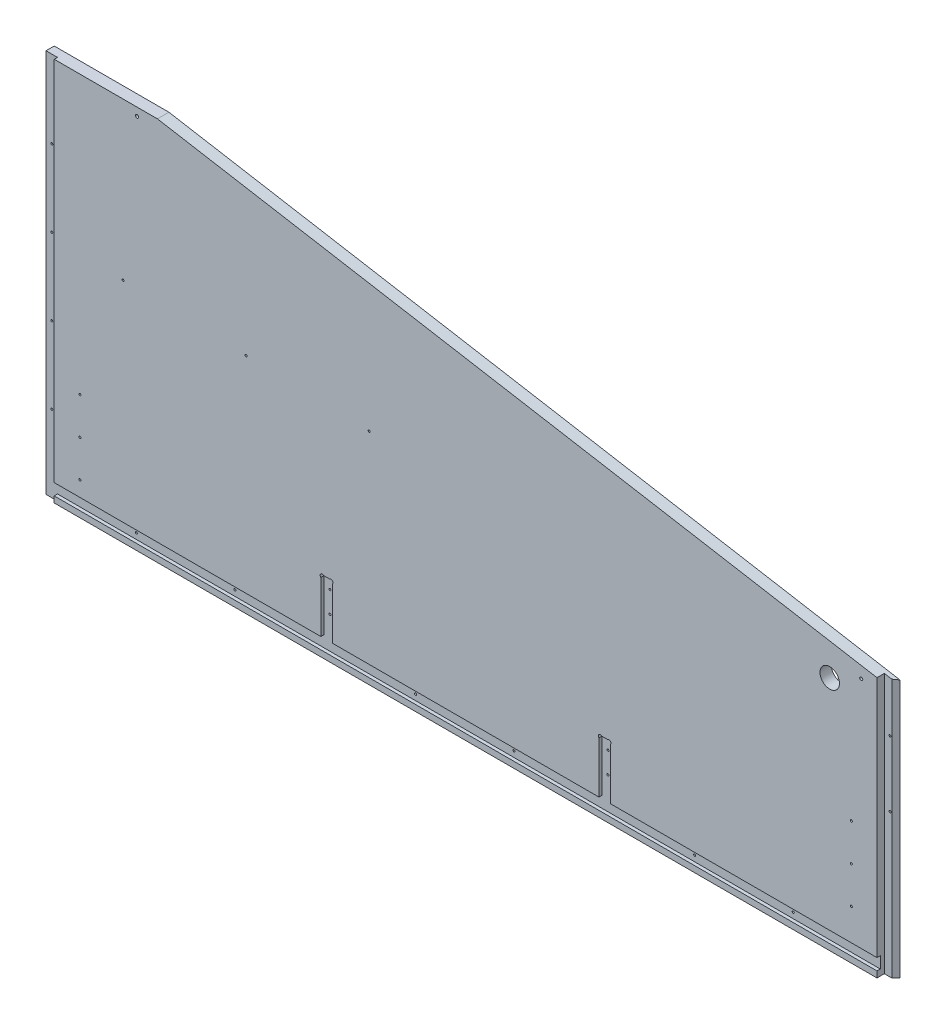
SolidWorks part; units mm, degrees
material "Maple"
ref_plane "Front Plane" through (0, 0, 0) normal (0, 0, 1) x (1, 0, 0)
ref_plane "Top Plane" through (0, 0, 0) normal (0, 1, 0) x (1, 0, 0)
ref_plane "Right Plane" through (0, 0, 0) normal (1, 0, 0) x (0, 0, -1)
sketch "Sketch1" plane through (0, 0, 0) normal (0, 0, 1) x (1, 0, 0)
  line L0 (8932.6508, -5243.5125) -> (10226.1458, -5243.5125)
  line L1 (9086.3208, -4722.0918) -> (10222.9708, -4853.7812)
  line L2 (8914.8708, -6342.0625) -> (10197.5708, -6342.0625)
  line L3 (8914.8708, -5808.6625) -> (10197.5708, -5808.6625)
  line L4 (8919.6333, -5253.0375) -> (10218.2083, -5253.0375)
  line L5 (9134.2633, -4656.1375) -> (9134.2633, -4638.3575)
  line L6 (9091.0833, -4638.3575) -> (9134.2633, -4638.3575)
  line L7 (9091.0833, -4567.2375) -> (9091.0833, -4638.3575)
  line L8 (9134.2633, -4656.1375) -> (9581.3033, -4656.1375)
  line L9 (9091.0833, -4567.2375) -> (9624.4833, -4567.2375)
  line L10 (9581.3033, -4656.1375) -> (9581.3033, -4638.3575)
  line L11 (9581.3033, -4638.3575) -> (9624.4833, -4638.3575)
  line L12 (9624.4833, -4567.2375) -> (9624.4833, -4638.3575)
  line L13 (8932.6508, -5225.7325) -> (9344.9775, -5225.7325)
  line L14 (8932.6508, -5256.2125) -> (8932.6508, -5243.5125)
  line L15 (8911.6958, -5256.2125) -> (8932.6508, -5256.2125)
  line L16 (8914.8708, -4722.0918) -> (9086.3208, -4722.0918)
  line L17 (8911.6958, -4715.5913) -> (8932.6508, -4715.5913)
  line L18 (8914.8708, -6342.0625) -> (8914.8708, -5808.6625)
  line L19 (12082.9917, -4722.0918) -> (10946.3417, -4853.7812)
  line L20 (12236.6617, -5243.5125) -> (10943.1667, -5243.5125)
  line L21 (10951.1042, -5253.0375) -> (12249.6792, -5253.0375)
  line L22 (10838.3917, -5656.2625) -> (11308.2917, -5656.2625)
  line L23 (10838.3917, -5719.7625) -> (11308.2917, -5719.7625)
  line L24 (10838.3917, -5742.5368) -> (11308.2917, -5742.5368)
  line L25 (10806.6417, -6342.0625) -> (11340.0417, -6342.0625)
  line L26 (10803.4667, -6335.7125) -> (11343.2167, -6335.7125)
  line L27 (10803.4667, -6317.9325) -> (11343.2167, -6317.9325)
  line L28 (10943.1667, -5225.7325) -> (11376.4483, -5225.7325)
  line L29 (11506.7292, -4754.5625) -> (10806.6417, -4827.5875)
  line L30 (11506.7292, -4567.2375) -> (11506.7292, -4754.5625)
  line L31 (10806.6417, -4567.2375) -> (10806.6417, -4827.5875)
  line L32 (10806.6417, -4567.2375) -> (11506.7292, -4567.2375)
  line L33 (10235.6708, -6329.3625) -> (10245.1958, -6329.3625)
  line L34 (10245.1958, -6329.3625) -> (10254.7208, -6278.5625)
  line L35 (10302.3458, -6329.3625) -> (10311.8708, -6278.5625)
  line L36 (10302.3458, -6329.3625) -> (10292.8208, -6329.3625)
  line L37 (10245.1958, -5821.3625) -> (10254.7208, -5872.1625)
  line L38 (10235.6708, -5821.3625) -> (10245.1958, -5821.3625)
  line L39 (10292.8208, -5821.3625) -> (10302.3458, -5821.3625)
  line L40 (10302.3458, -5821.3625) -> (10311.8708, -5872.1625)
  line L41 (10235.6708, -5821.3625) -> (10235.6708, -6329.3625)
  line L42 (10254.7208, -5872.1625) -> (10254.7208, -6278.5625)
  line L43 (10311.8708, -5872.1625) -> (10311.8708, -6278.5625)
  line L44 (10292.8208, -5821.3625) -> (10292.8208, -6329.3625)
  line L45 (8932.6508, -5225.7325) -> (8932.6508, -4715.5913)
  line L46 (8911.6958, -4715.5913) -> (8911.6958, -5256.2125)
  line L47 (8914.8708, -5248.275) -> (8914.8708, -4722.0918)
  line L48 (8919.6333, -5253.0375) -> (8914.8708, -5248.275)
  line L49 (8914.8708, -5145.0875) -> (8937.426, -5145.0875)
  line L50 (8914.8708, -5202.2375) -> (8937.426, -5202.2375)
  line L51 (10838.3917, -5656.2625) -> (10838.3917, -5719.7625)
  line L52 (10832.0417, -5736.1868) -> (10856.1717, -5736.1868)
  line L53 (10806.6417, -6342.0625) -> (10806.6417, -5818.7368)
  line L54 (10832.0417, -5649.9125) -> (10856.1717, -5649.9125)
  line L55 (10832.0417, -5726.1125) -> (10856.1717, -5726.1125)
  line L56 (10806.6417, -5818.7368) -> (10833.9015, -5818.7368)
  line L57 (10832.0417, -5806.0442) -> (10851.6815, -5806.0442)
  line L58 (10856.1717, -5801.5541) -> (10856.1717, -5736.1868)
  line L59 (10838.3917, -5814.2467) -> (10838.3917, -5742.5368)
  line L60 (10832.0417, -5806.0442) -> (10832.0417, -5736.1868)
  line L61 (10803.4667, -6317.9325) -> (10803.4667, -6335.7125)
  line L62 (10197.5708, -5808.6625) -> (10197.5708, -6342.0625)
  line L63 (9762.3842, -6348.4125) -> (9762.3842, -5802.3125)
  line L64 (9780.1642, -6348.4125) -> (9762.3842, -6348.4125)
  line L65 (9780.1642, -5802.3125) -> (9780.1642, -6348.4125)
  line L66 (9762.3842, -5802.3125) -> (9780.1642, -5802.3125)
  line L67 (9332.2775, -6348.4125) -> (9332.2775, -5802.3125)
  line L68 (9332.2775, -6348.4125) -> (9350.0575, -6348.4125)
  line L69 (9350.0575, -5802.3125) -> (9350.0575, -6348.4125)
  line L70 (9332.2775, -5802.3125) -> (9350.0575, -5802.3125)
  line L71 (9993.8374, -6061.075) -> (9993.8374, -6045.2418)
  line L72 (9998.5999, -6065.8375) -> (10014.4331, -6065.8375)
  line L73 (9998.5999, -6084.8875) -> (10014.4331, -6084.8875)
  line L74 (9993.8374, -6105.4832) -> (9993.8374, -6089.65)
  line L75 (9974.7874, -6105.4832) -> (9974.7874, -6089.65)
  line L76 (9954.1917, -6084.8875) -> (9970.0249, -6084.8875)
  line L77 (9974.7874, -6061.075) -> (9974.7874, -6045.2418)
  line L78 (9954.1917, -6065.8375) -> (9970.0249, -6065.8375)
  line L79 (10793.9417, -6237.2875) -> (10816.4969, -6237.2875)
  line L80 (10793.9417, -6294.4375) -> (10816.4969, -6294.4375)
  line L81 (10856.1717, -5649.9125) -> (10856.1717, -5726.1125)
  line L82 (10832.0417, -5726.1125) -> (10832.0417, -5649.9125)
  line L83 (10226.1458, -5225.7325) -> (10226.1458, -5243.5125)
  line L84 (10205.1908, -5257.8) -> (10205.1908, -4844.2499)
  line L85 (10230.9083, -4844.2499) -> (10230.9083, -5257.8)
  line L86 (10205.1908, -5257.8) -> (10230.9083, -5257.8)
  line L87 (10205.1908, -4844.2499) -> (10230.9083, -4844.2499)
  line L88 (10946.3417, -5176.8375) -> (10968.8969, -5176.8375)
  line L89 (9349.4676, -5141.9125) -> (9358.2674, -5141.9125)
  line L90 (10946.3417, -5119.6875) -> (10968.8969, -5119.6875)
  line L91 (9929.011, -4660.9635) -> (10066.0807, -4660.9635)
  line L92 (9929.011, -4678.7435) -> (10066.0807, -4678.7435)
  line L93 (10943.1667, -5225.7325) -> (10943.1667, -5243.5125)
  line L94 (10946.3417, -5248.275) -> (10951.1042, -5253.0375)
  line L95 (10946.3417, -5257.8063) -> (10946.3417, -4849.0188)
  line L96 (10964.1217, -5257.8) -> (10964.1217, -4844.2499)
  line L97 (10938.4042, -4844.2499) -> (10938.4042, -5257.8)
  line L98 (10938.4042, -5257.8) -> (10964.1217, -5257.8)
  line L99 (10964.1217, -4844.2499) -> (10938.4042, -4844.2499)
  line L100 (10344.8908, -4560.8875) -> (10369.0208, -4560.8875)
  line L101 (10344.8908, -4560.8875) -> (10369.0208, -4560.8875)
  line L102 (10800.2917, -4560.8875) -> (10824.4217, -4560.8875)
  line L103 (10200.4156, -5119.6875) -> (10222.9708, -5119.6875)
  line L104 (10200.4156, -5176.8375) -> (10222.9708, -5176.8375)
  line L105 (9344.9775, -5146.4026) -> (9344.9775, -5225.7325)
  line L106 (10344.8908, -4560.8875) -> (10344.8908, -4833.9375)
  line L107 (9792.8642, -5225.7325) -> (9792.8642, -5146.4026)
  line L108 (9362.7575, -5225.7325) -> (9775.0842, -5225.7325)
  line L109 (9680.3633, -4761.8396) -> (9680.3633, -4559.9604)
  line L110 (9656.2333, -4559.9604) -> (9680.3633, -4559.9604)
  line L111 (9656.2333, -4761.8396) -> (9680.3633, -4761.8396)
  line L112 (9656.2333, -4761.8396) -> (9656.2333, -4559.9604)
  line L113 (9779.5743, -5141.9125) -> (9788.374, -5141.9125)
  line L114 (10070.5708, -4665.4536) -> (10070.5708, -4674.2534)
  line L115 (9924.5208, -4674.2534) -> (9924.5208, -4665.4536)
  line L116 (12127.4417, -6188.3925) -> (12205.5015, -6188.3925)
  line L117 (12209.9917, -6170.6125) -> (12209.9917, -6183.9024)
  line L118 (9792.8642, -5225.7325) -> (10226.1458, -5225.7325)
  line L119 (9662.5833, -4754.5625) -> (10362.6708, -4827.5875)
  line L120 (9662.5833, -4567.2375) -> (9662.5833, -4754.5625)
  line L121 (10362.6708, -4567.2375) -> (10362.6708, -4827.5875)
  line L122 (9662.5833, -4567.2375) -> (10362.6708, -4567.2375)
  line L123 (10824.4217, -4833.9375) -> (10800.2917, -4833.9375)
  line L124 (10800.2917, -4833.9375) -> (10800.2917, -4560.8875)
  line L125 (10824.4217, -4560.8875) -> (10824.4217, -4833.9375)
  line L126 (10344.8908, -4833.9375) -> (10369.0208, -4833.9375)
  line L127 (10369.0208, -4833.9375) -> (10369.0208, -4560.8875)
  line L128 (10222.9708, -5248.275) -> (10218.2083, -5253.0375)
  line L129 (10222.9708, -5257.8063) -> (10222.9708, -4849.0188)
  line L130 (11734.6544, -5701.375) -> (11739.2301, -5701.375)
  line L131 (9362.7575, -5225.7325) -> (9362.7575, -5146.4026)
  line L132 (9775.0842, -5146.4026) -> (9775.0842, -5225.7325)
  line L133 (11761.3864, -5701.375) -> (11756.8282, -5701.375)
  line L134 (11734.6544, -5693.755) -> (11739.2301, -5693.755)
  line L135 (11761.4039, -5693.755) -> (11756.8282, -5693.755)
  line L136 (11734.6544, -5701.375) -> (11739.2301, -5701.375)
  line L137 (11744.3462, -5721.3024) -> (11744.3462, -5706.4179)
  line L138 (11751.7122, -5721.3024) -> (11751.7122, -5706.4179)
  line L139 (11740.0917, -6170.6125) -> (11740.0917, -6183.9024)
  line L140 (11689.2917, -6188.3925) -> (11822.6417, -6188.3925)
  line L141 (11689.2917, -6348.4093) -> (11689.2917, -6164.2657)
  line L142 (11689.2917, -6164.2657) -> (11746.4417, -6164.2657)
  line L143 (11746.4417, -6164.2657) -> (11746.4417, -6188.3925)
  line L144 (11689.2917, -6164.2657) -> (11746.4417, -6164.2657)
  line L145 (11340.0417, -5818.7368) -> (11340.0417, -6342.0625)
  line L146 (11290.5117, -5726.1125) -> (11314.6417, -5726.1125)
  line L147 (11290.5117, -5649.9125) -> (11290.5117, -5726.1125)
  line L148 (11340.0417, -5818.7368) -> (11312.7818, -5818.7368)
  line L149 (11314.6417, -5806.0442) -> (11295.0018, -5806.0442)
  line L150 (11290.5117, -5801.5541) -> (11290.5117, -5736.1868)
  line L151 (11308.2917, -5814.2467) -> (11308.2917, -5742.5368)
  line L152 (11314.6417, -5806.0442) -> (11314.6417, -5736.1868)
  line L153 (11290.5117, -5736.1868) -> (11314.6417, -5736.1868)
  line L154 (11848.0417, -6267.1325) -> (11962.3417, -6267.1325)
  line L155 (11962.3417, -6267.1325) -> (11962.3417, -6203.6325)
  line L156 (11343.2167, -6317.9325) -> (11343.2167, -6335.7125)
  line L157 (11365.4417, -5656.2625) -> (11365.4417, -5719.7625)
  line L158 (11365.4417, -5656.2625) -> (11479.7417, -5656.2625)
  line L159 (11778.1917, -6071.3937) -> (11802.3217, -6071.3937)
  line L160 (11314.6417, -5726.1125) -> (11314.6417, -5649.9125)
  line L161 (11314.6417, -5649.9125) -> (11290.5117, -5649.9125)
  line L162 (11308.2917, -5719.7625) -> (11308.2917, -5656.2625)
  line L163 (11689.2917, -6348.4093) -> (11713.4217, -6348.4093)
  line L164 (12203.6417, -6164.2657) -> (12260.7917, -6164.2657)
  line L165 (11713.4217, -6348.4093) -> (11713.4217, -6164.2657)
  line L166 (11695.6417, -6342.0625) -> (11695.6417, -6170.6125)
  line L167 (11695.6417, -6048.5337) -> (11699.4517, -6052.3437)
  line L168 (11822.6417, -6292.5325) -> (11822.6417, -6188.3925)
  line L169 (11695.6417, -6342.0625) -> (11695.6417, -6170.6125)
  line L170 (11848.0417, -6203.6325) -> (11962.3417, -6203.6325)
  line L171 (11848.0417, -6203.6325) -> (11848.0417, -6267.1325)
  line L172 (11987.7417, -6267.1325) -> (11987.7417, -6203.6325)
  line L173 (11784.5417, -6077.7437) -> (11784.5417, -6141.2438)
  line L174 (11517.8417, -5656.2625) -> (11632.1417, -5656.2625)
  line L175 (11632.1417, -5656.2625) -> (11632.1417, -5719.7625)
  line L176 (11632.1417, -5719.7625) -> (11517.8417, -5719.7625)
  line L177 (11517.8417, -5719.7625) -> (11517.8417, -5656.2625)
  line L178 (11692.4667, -6028.2137) -> (11692.4667, -6045.9937)
  line L179 (11695.6417, -5979.3188) -> (11718.1969, -5979.3188)
  line L180 (11695.6417, -5922.1687) -> (11718.1969, -5922.1687)
  line L181 (11821.0415, -5722.9375) -> (11821.0415, -5943.6)
  line L182 (11687.7042, -5651.5) -> (11701.9917, -5651.5)
  line L183 (11687.7042, -5651.5) -> (11687.7042, -6055.5251)
  line L184 (11687.7042, -6055.5251) -> (11701.9917, -6055.5251)
  line L185 (11701.9917, -6055.5251) -> (11701.9917, -5651.5)
  line L186 (11695.6417, -6055.2013) -> (11695.6417, -5649.595)
  line L187 (11695.6417, -5656.2625) -> (11695.6417, -6048.5337)
  line L188 (11695.6417, -6170.6125) -> (11740.0917, -6170.6125)
  line L189 (12203.6417, -6164.2657) -> (12203.6417, -6188.3925)
  line L190 (12254.4417, -6342.0625) -> (12254.4417, -6170.6125)
  line L191 (12129.0419, -5943.6) -> (12129.0419, -5722.9375)
  line L192 (12254.4417, -6048.5337) -> (12250.6317, -6052.3437)
  line L193 (12257.6167, -6045.9937) -> (12257.6167, -6028.2137)
  line L194 (12248.0917, -5651.5) -> (12262.3792, -5651.5)
  line L195 (12262.3792, -5651.5) -> (12262.3792, -6055.5251)
  line L196 (12262.3792, -6055.5251) -> (12248.0917, -6055.5251)
  line L197 (12248.0917, -6055.5251) -> (12248.0917, -5651.5)
  line L198 (12254.4417, -6141.2438) -> (12254.4417, -6077.7437)
  line L199 (12236.6617, -6164.2657) -> (12260.7917, -6164.2657)
  line L200 (12102.0417, -6267.1325) -> (11987.7417, -6267.1325)
  line L201 (11330.1865, -6237.2875) -> (11352.7417, -6237.2875)
  line L202 (11330.1865, -6294.4375) -> (11352.7417, -6294.4375)
  line L203 (11474.6617, -5851.8425) -> (11492.4417, -5851.8425)
  line L204 (11474.6617, -5808.6625) -> (11474.6617, -5851.8425)
  line L205 (11403.5417, -5808.6625) -> (11474.6617, -5808.6625)
  line L206 (11492.4417, -5851.8425) -> (11492.4417, -6298.8825)
  line L207 (11403.5417, -6342.0625) -> (11403.5417, -5808.6625)
  line L208 (11474.6617, -6298.8825) -> (11492.4417, -6298.8825)
  line L209 (11474.6617, -6342.0625) -> (11474.6617, -6298.8825)
  line L210 (11403.5417, -6342.0625) -> (11474.6617, -6342.0625)
  line L211 (11619.4417, -5851.8425) -> (11601.6617, -5851.8425)
  line L212 (11601.6617, -5808.6625) -> (11601.6617, -5851.8425)
  line L213 (11530.5417, -5808.6625) -> (11601.6617, -5808.6625)
  line L214 (11619.4417, -5851.8425) -> (11619.4417, -6298.8825)
  line L215 (11530.5417, -6342.0625) -> (11530.5417, -5808.6625)
  line L216 (11619.4417, -6298.8825) -> (11601.6617, -6298.8825)
  line L217 (11601.6617, -6342.0625) -> (11601.6617, -6298.8825)
  line L218 (11530.5417, -6342.0625) -> (11601.6617, -6342.0625)
  line L219 (11479.7417, -5719.7625) -> (11479.7417, -5656.2625)
  line L220 (11365.4417, -5719.7625) -> (11479.7417, -5719.7625)
  line L221 (11778.1917, -6147.5937) -> (11802.3217, -6147.5937)
  line L222 (11802.3217, -6071.3937) -> (11802.3217, -6147.5937)
  line L223 (11778.1917, -6147.5937) -> (11778.1917, -6071.3937)
  line L224 (12254.4417, -5922.1687) -> (12231.8865, -5922.1687)
  line L225 (12254.4417, -5979.3188) -> (12231.8865, -5979.3188)
  line L226 (12254.4417, -6055.2013) -> (12254.4417, -5649.595)
  line L227 (12254.4417, -6048.5337) -> (12254.4417, -5656.2625)
  line L228 (11841.6917, -5702.2873) -> (12108.3917, -5702.2873)
  line L229 (11822.6417, -6292.5325) -> (12127.4417, -6292.5325)
  line L230 (12127.4417, -6292.5325) -> (12127.4417, -6188.3925)
  line L231 (12254.4417, -6170.6125) -> (12209.9917, -6170.6125)
  line L232 (11695.6417, -6342.0625) -> (12254.4417, -6342.0625)
  line L233 (12236.6617, -6348.4093) -> (12260.7917, -6348.4093)
  line L234 (12260.7917, -6348.4093) -> (12260.7917, -6164.2657)
  line L235 (12236.6617, -6348.4093) -> (12236.6617, -6164.2657)
  line L236 (12102.0417, -6203.6325) -> (12102.0417, -6267.1325)
  line L237 (11987.7417, -6203.6325) -> (12102.0417, -6203.6325)
  line L238 (12236.6617, -6147.5937) -> (12236.6617, -6071.3937)
  line L239 (12203.6417, -6188.3925) -> (12260.7917, -6188.3925)
  line L240 (11098.7417, -4665.4536) -> (11098.7417, -4674.2534)
  line L241 (11394.2283, -5146.4026) -> (11394.2283, -5225.7325)
  line L242 (11376.4483, -5225.7325) -> (11376.4483, -5146.4026)
  line L243 (11394.2283, -5225.7325) -> (11806.555, -5225.7325)
  line L244 (11841.6917, -5964.2502) -> (12108.3917, -5964.2502)
  line L245 (12236.6617, -6147.5937) -> (12260.7917, -6147.5937)
  line L246 (12236.6617, -5256.2125) -> (12236.6617, -5243.5125)
  line L247 (12260.7917, -6147.5937) -> (12260.7917, -6071.3937)
  line L248 (12260.7917, -6071.3937) -> (12236.6617, -6071.3937)
  line L249 (12254.4417, -6077.7437) -> (11784.5417, -6077.7437)
  line L250 (11784.5417, -6141.2438) -> (12254.4417, -6141.2438)
  line L252 (12254.4417, -5656.2625) -> (11695.6417, -5656.2625)
  line L253 (11699.4517, -6052.3437) -> (12250.6317, -6052.3437)
  line L254 (11692.4667, -6045.9937) -> (12257.6167, -6045.9937)
  line L255 (11692.4667, -6028.2137) -> (12257.6167, -6028.2137)
  line L256 (11824.335, -5146.4026) -> (11824.335, -5225.7325)
  line L257 (11811.0451, -5141.9125) -> (11819.8449, -5141.9125)
  line L258 (11244.7917, -4674.2534) -> (11244.7917, -4665.4536)
  line L259 (11806.555, -5225.7325) -> (11806.555, -5146.4026)
  line L260 (11488.9492, -4761.8396) -> (11488.9492, -4559.9604)
  line L261 (11488.9492, -4559.9604) -> (11513.0792, -4559.9604)
  line L262 (11488.9492, -4761.8396) -> (11513.0792, -4761.8396)
  line L263 (11513.0792, -4761.8396) -> (11513.0792, -4559.9604)
  line L264 (11240.3015, -4660.9635) -> (11103.2318, -4660.9635)
  line L265 (11103.2318, -4678.7435) -> (11240.3015, -4678.7435)
  line L266 (12236.6617, -5225.7325) -> (12236.6617, -4715.5913)
  line L267 (12257.6167, -4715.5913) -> (12257.6167, -5256.2125)
  line L268 (12254.4417, -5248.275) -> (12254.4417, -4722.0918)
  line L269 (12236.6617, -5225.7325) -> (11824.335, -5225.7325)
  line L270 (12035.0492, -4656.1375) -> (12035.0492, -4638.3575)
  line L271 (12078.2292, -4638.3575) -> (12035.0492, -4638.3575)
  line L272 (12078.2292, -4567.2375) -> (12078.2292, -4638.3575)
  line L273 (12035.0492, -4656.1375) -> (11588.0092, -4656.1375)
  line L274 (11544.8292, -4567.2375) -> (12078.2292, -4567.2375)
  line L275 (11588.0092, -4656.1375) -> (11588.0092, -4638.3575)
  line L276 (11544.8292, -4638.3575) -> (11588.0092, -4638.3575)
  line L277 (11544.8292, -4567.2375) -> (11544.8292, -4638.3575)
  line L278 (12249.6792, -5253.0375) -> (12254.4417, -5248.275)
  line L280 (12257.6167, -5256.2125) -> (12236.6617, -5256.2125)
  line L281 (12231.8865, -5145.0875) -> (12254.4417, -5145.0875)
  line L282 (12231.8865, -5202.2375) -> (12254.4417, -5202.2375)
  line L283 (12236.6617, -4715.5913) -> (12257.6167, -4715.5913)
  line L284 (12082.9917, -4722.0918) -> (12254.4417, -4722.0918)
  line L285 (11380.9385, -5141.9125) -> (11389.7382, -5141.9125)
  circle A0 centre (8923.7608, -4778.9042) radius 1.5875
  circle A1 centre (9062.6598, -4736.3765) radius 2.3685
  circle A2 centre (9051.3958, -6281.7375) radius 22.225
  circle A3 centre (9083.1458, -6249.9875) radius 1.5875
  circle A4 centre (9083.1458, -6313.4875) radius 1.5875
  circle A5 centre (9019.6458, -6249.9875) radius 1.5875
  circle A6 centre (9019.6458, -6313.4875) radius 1.5875
  circle A7 centre (8972.3383, -5202.2375) radius 1.5875
  circle A8 centre (8923.7608, -5015.9708) radius 1.5875
  circle A9 centre (8923.7608, -5134.5042) radius 1.5875
  circle A10 centre (9054.5708, -5234.6225) radius 1.5875
  circle A11 centre (8923.7608, -4897.4375) radius 1.5875
  circle A12 centre (8972.3383, -5087.9375) radius 1.5875
  circle A13 centre (8972.3383, -5145.0875) radius 1.5875
  circle A14 centre (10847.2817, -5668.9625) radius 1.5875
  circle A15 centre (10847.2817, -5707.0625) radius 1.5875
  circle A16 centre (10847.2817, -5755.2368) radius 1.5875
  circle A17 centre (10851.4092, -6237.2875) radius 1.5875
  circle A18 centre (10851.4092, -6294.4375) radius 1.5875
  circle A19 centre (10847.2817, -5793.3442) radius 1.5875
  arc A20 (10833.9015, -5818.7368) -> (10838.3917, -5814.2467) centre (10836.1466, -5816.4918) ccw
  arc A21 (10851.6815, -5806.0442) -> (10856.1717, -5801.5541) centre (10853.9266, -5803.7992) ccw
  circle A22 centre (10882.8417, -6040.4375) radius 1.5875
  circle A23 centre (10882.8417, -6218.2375) radius 1.5875
  circle A24 centre (10882.8417, -5862.6375) radius 1.5875
  circle A25 centre (10908.2417, -6326.8225) radius 1.5875
  circle A26 centre (10908.2417, -6326.8225) radius 1.5875
  circle A27 centre (10851.4092, -6180.1375) radius 1.5875
  circle A28 centre (10815.5317, -4783.4231) radius 1.5875
  circle A29 centre (10815.5317, -4696.9488) radius 1.5875
  circle A30 centre (10815.5317, -4610.4746) radius 1.5875
  circle A31 centre (10979.1323, -4867.0082) radius 2.3685
  circle A32 centre (10190.1802, -4867.0082) radius 2.3685
  circle A33 centre (10955.2317, -4929.9812) radius 1.5875
  circle A34 centre (10955.2317, -5031.5812) radius 1.5875
  circle A35 centre (10214.0808, -4929.9812) radius 1.5875
  circle A36 centre (10214.0808, -5031.5812) radius 1.5875
  circle A37 centre (9341.1675, -6265.8625) radius 1.5875
  circle A38 centre (9771.2742, -5884.8625) radius 1.5875
  circle A39 centre (9771.2742, -6138.8625) radius 1.5875
  circle A40 centre (9771.2742, -6011.8625) radius 1.5875
  arc A41 (10036.2287, -6113.8083) -> (10051.3426, -6111.6033) centre (10042.9639, -6107.0732) ccw
  arc A42 (10051.3426, -6111.6033) -> (10051.3426, -6039.1217) centre (9984.3124, -6075.3625) ccw
  arc A43 (10051.3426, -6039.1217) -> (10036.2287, -6036.9167) centre (10042.9639, -6043.6518) ccw
  arc A44 (10034.5851, -6102.5431) -> (10034.5851, -6048.1819) centre (9984.3124, -6075.3625) ccw
  arc A45 (10034.5851, -6102.5431) -> (10036.2287, -6113.8083) centre (10042.9639, -6107.0732) ccw
  arc A46 (10036.2287, -6036.9167) -> (10034.5851, -6048.1819) centre (10042.9639, -6043.6518) ccw
  arc A47 (9945.8666, -6127.2787) -> (9948.0717, -6142.3927) centre (9952.6018, -6134.0139) ccw
  arc A48 (9948.0717, -6142.3927) -> (10020.5532, -6142.3927) centre (9984.3124, -6075.3625) ccw
  arc A49 (10020.5532, -6142.3927) -> (10022.7583, -6127.2787) centre (10016.0231, -6134.0139) ccw
  arc A50 (9957.1319, -6125.6352) -> (10011.493, -6125.6352) centre (9984.3124, -6075.3625) ccw
  arc A51 (9957.1319, -6125.6352) -> (9945.8666, -6127.2787) centre (9952.6018, -6134.0139) ccw
  arc A52 (10022.7583, -6127.2787) -> (10011.493, -6125.6352) centre (10016.0231, -6134.0139) ccw
  arc A53 (9932.3962, -6036.9167) -> (9917.2822, -6039.1217) centre (9925.661, -6043.6518) ccw
  arc A54 (9917.2822, -6039.1217) -> (9917.2822, -6111.6033) centre (9984.3124, -6075.3625) ccw
  arc A55 (9917.2822, -6111.6033) -> (9932.3962, -6113.8083) centre (9925.661, -6107.0732) ccw
  arc A56 (9934.0398, -6048.1819) -> (9934.0398, -6102.5431) centre (9984.3124, -6075.3625) ccw
  arc A57 (9934.0398, -6048.1819) -> (9932.3962, -6036.9167) centre (9925.661, -6043.6518) ccw
  arc A58 (9932.3962, -6113.8083) -> (9934.0398, -6102.5431) centre (9925.661, -6107.0732) ccw
  arc A59 (9945.8666, -6023.4463) -> (9957.1319, -6025.0898) centre (9952.6018, -6016.7111) ccw
  arc A60 (10011.493, -6025.0898) -> (10022.7583, -6023.4463) centre (10016.0231, -6016.7111) ccw
  arc A61 (10011.493, -6025.0898) -> (9957.1319, -6025.0898) centre (9984.3124, -6075.3625) ccw
  arc A62 (9948.0717, -6008.3323) -> (9945.8666, -6023.4463) centre (9952.6018, -6016.7111) ccw
  arc A63 (10020.5532, -6008.3323) -> (9948.0717, -6008.3323) centre (9984.3124, -6075.3625) ccw
  arc A64 (10022.7583, -6023.4463) -> (10020.5532, -6008.3323) centre (10016.0231, -6016.7111) ccw
  arc A65 (10005.0943, -6187.7574) -> (10096.7073, -6096.1443) centre (9984.3124, -6075.3625) ccw
  arc A66 (9993.8374, -6178.3911) -> (10005.0943, -6187.7574) centre (10003.3624, -6178.3911) ccw
  arc A67 (10001.6306, -6169.0249) -> (10077.9748, -6092.6807) centre (9984.3124, -6075.3625) ccw
  arc A68 (10087.3411, -6084.8875) -> (10077.9748, -6092.6807) centre (10087.3411, -6094.4125) ccw
  arc A69 (10001.6306, -6169.0249) -> (9993.8374, -6178.3911) centre (10003.3624, -6178.3911) ccw
  arc A70 (9963.5306, -6187.7574) -> (9974.7874, -6178.3911) centre (9965.2624, -6178.3911) ccw
  arc A71 (9871.9176, -6096.1443) -> (9963.5306, -6187.7574) centre (9984.3124, -6075.3625) ccw
  arc A72 (9881.2838, -6084.8875) -> (9871.9176, -6096.1443) centre (9881.2838, -6094.4125) ccw
  arc A73 (9890.65, -6092.6807) -> (9966.9943, -6169.0249) centre (9984.3124, -6075.3625) ccw
  arc A74 (9974.7874, -6178.3911) -> (9966.9943, -6169.0249) centre (9965.2624, -6178.3911) ccw
  arc A75 (9890.65, -6092.6807) -> (9881.2838, -6084.8875) centre (9881.2838, -6094.4125) ccw
  arc A76 (9871.9176, -6054.5807) -> (9881.2838, -6065.8375) centre (9881.2838, -6056.3125) ccw
  arc A77 (9963.5306, -5962.9676) -> (9871.9176, -6054.5807) centre (9984.3124, -6075.3625) ccw
  arc A78 (9974.7874, -5972.3339) -> (9963.5306, -5962.9676) centre (9965.2624, -5972.3339) ccw
  arc A79 (9966.9943, -5981.7001) -> (9890.65, -6058.0443) centre (9984.3124, -6075.3625) ccw
  arc A80 (9881.2838, -6065.8375) -> (9890.65, -6058.0443) centre (9881.2838, -6056.3125) ccw
  arc A81 (9966.9943, -5981.7001) -> (9974.7874, -5972.3339) centre (9965.2624, -5972.3339) ccw
  arc A82 (10077.9748, -6058.0443) -> (10087.3411, -6065.8375) centre (10087.3411, -6056.3125) ccw
  arc A83 (9993.8374, -5972.3339) -> (10001.6306, -5981.7001) centre (10003.3624, -5972.3339) ccw
  arc A84 (10077.9748, -6058.0443) -> (10001.6306, -5981.7001) centre (9984.3124, -6075.3625) ccw
  arc A85 (10087.3411, -6065.8375) -> (10096.7073, -6054.5807) centre (10087.3411, -6056.3125) ccw
  arc A86 (10096.7073, -6054.5807) -> (10005.0943, -5962.9676) centre (9984.3124, -6075.3625) ccw
  arc A87 (10005.0943, -5962.9676) -> (9993.8374, -5972.3339) centre (10003.3624, -5972.3339) ccw
  arc A88 (10014.4331, -6065.8375) -> (10018.7361, -6059.0339) centre (10014.4331, -6061.075) ccw
  arc A89 (10018.7361, -6059.0339) -> (10000.641, -6040.9388) centre (9984.3124, -6075.3625) ccw
  arc A90 (10000.641, -6040.9388) -> (9993.8374, -6045.2418) centre (9998.5999, -6045.2418) ccw
  arc A91 (9993.8374, -6061.075) -> (9998.5999, -6065.8375) centre (9998.5999, -6061.075) ccw
  arc A92 (9993.8374, -6105.4832) -> (10000.641, -6109.7862) centre (9998.5999, -6105.4832) ccw
  arc A93 (10000.641, -6109.7862) -> (10018.7361, -6091.6911) centre (9984.3124, -6075.3625) ccw
  arc A94 (10018.7361, -6091.6911) -> (10014.4331, -6084.8875) centre (10014.4331, -6089.65) ccw
  arc A95 (9998.5999, -6084.8875) -> (9993.8374, -6089.65) centre (9998.5999, -6089.65) ccw
  arc A96 (9954.1917, -6084.8875) -> (9949.8888, -6091.6911) centre (9954.1917, -6089.65) ccw
  arc A97 (9949.8888, -6091.6911) -> (9967.9839, -6109.7862) centre (9984.3124, -6075.3625) ccw
  arc A98 (9967.9839, -6109.7862) -> (9974.7874, -6105.4832) centre (9970.0249, -6105.4832) ccw
  arc A99 (9974.7874, -6089.65) -> (9970.0249, -6084.8875) centre (9970.0249, -6089.65) ccw
  arc A100 (9970.0249, -6065.8375) -> (9974.7874, -6061.075) centre (9970.0249, -6061.075) ccw
  arc A101 (9949.8888, -6059.0339) -> (9954.1917, -6065.8375) centre (9954.1917, -6061.075) ccw
  arc A102 (9967.9839, -6040.9388) -> (9949.8888, -6059.0339) centre (9984.3124, -6075.3625) ccw
  arc A103 (9974.7874, -6045.2418) -> (9967.9839, -6040.9388) centre (9970.0249, -6045.2418) ccw
  arc A104 (10096.7073, -6096.1443) -> (10087.3411, -6084.8875) centre (10087.3411, -6094.4125) ccw
  circle A105 centre (9771.2742, -6265.8625) radius 1.5875
  circle A106 centre (9341.1675, -5884.8625) radius 1.5875
  circle A107 centre (9341.1675, -6138.8625) radius 1.5875
  circle A108 centre (9341.1675, -6011.8625) radius 1.5875
  circle A109 centre (11037.2315, -4887.5494) radius 15.0812
  arc A110 (9349.4676, -5141.9125) -> (9344.9775, -5146.4026) centre (9347.2226, -5144.1576) ccw
  arc A111 (9362.7575, -5146.4026) -> (9358.2674, -5141.9125) centre (9360.5124, -5144.1576) ccw
  circle A112 centre (9946.7458, -4669.8535) radius 1.5875
  arc A113 (9924.5208, -4674.2534) -> (9929.011, -4678.7435) centre (9926.7659, -4676.4984) ccw
  circle A114 centre (11003.8092, -5176.8375) radius 1.5875
  circle A115 centre (11003.8092, -5119.6875) radius 1.5875
  circle A116 centre (10353.7808, -4696.9488) radius 1.5875
  circle A117 centre (10353.7808, -4610.4746) radius 1.5875
  circle A118 centre (10353.7808, -4783.4231) radius 1.5875
  circle A119 centre (11003.8092, -5062.5375) radius 1.5875
  circle A120 centre (9353.8675, -5160.9625) radius 1.5875
  circle A121 centre (9638.7708, -5234.6225) radius 1.5875
  circle A122 centre (9671.4733, -4724.1144) radius 1.5875
  circle A123 centre (9671.4733, -4661.3637) radius 1.5875
  circle A124 centre (9671.4733, -4598.6129) radius 1.5875
  arc A125 (9792.8642, -5146.4026) -> (9788.374, -5141.9125) centre (9790.6191, -5144.1576) ccw
  arc A126 (9779.5743, -5141.9125) -> (9775.0842, -5146.4026) centre (9777.3292, -5144.1576) ccw
  circle A127 centre (10048.3458, -4669.8535) radius 1.5875
  arc A128 (10070.5708, -4665.4536) -> (10066.0807, -4660.9635) centre (10068.3258, -4663.2086) ccw
  arc A129 (10066.0807, -4678.7435) -> (10070.5708, -4674.2534) centre (10068.3258, -4676.4984) ccw
  circle A130 centre (9997.5458, -4669.8535) radius 1.5875
  arc A131 (9929.011, -4660.9635) -> (9924.5208, -4665.4536) centre (9926.7659, -4663.2086) ccw
  circle A132 centre (10132.081, -4887.5494) radius 15.0812
  circle A133 centre (10165.5033, -5176.8375) radius 1.5875
  circle A134 centre (10165.5033, -5119.6875) radius 1.5875
  circle A135 centre (9486.3708, -5234.6225) radius 1.5875
  circle A136 centre (10165.5033, -5062.5375) radius 1.5875
  circle A137 centre (9206.9708, -5234.6225) radius 1.5875
  circle A138 centre (10070.5708, -5234.6225) radius 1.5875
  circle A139 centre (9918.1708, -5234.6225) radius 1.5875
  circle A140 centre (9783.9742, -5160.9625) radius 1.5875
  circle A141 centre (9783.9742, -5193.9825) radius 1.5875
  circle A142 centre (9353.8675, -5193.9825) radius 1.5875
  circle A143 centre (11073.3417, -6326.8225) radius 1.5875
  circle A144 centre (11073.3417, -6326.8225) radius 1.5875
  circle A145 centre (11295.2742, -6180.1375) radius 1.5875
  circle A146 centre (11295.2742, -6294.4375) radius 1.5875
  circle A147 centre (11295.2742, -6237.2875) radius 1.5875
  circle A148 centre (11975.0417, -5692.775) radius 3.4925
  circle A149 centre (11263.8417, -5862.6375) radius 1.5875
  arc A150 (11739.2301, -5701.375) -> (11744.3462, -5706.4179) centre (11748.0292, -5697.565) ccw
  arc A151 (11751.7122, -5706.4179) -> (11756.8282, -5701.375) centre (11748.0292, -5697.565) ccw
  arc A152 (11744.3462, -5721.3024) -> (11751.7122, -5721.3024) centre (11748.0292, -5725.505) ccw
  arc A153 (11734.6544, -5693.755) -> (11724.9787, -5697.565) centre (11730.5667, -5697.565) ccw
  arc A154 (11756.8282, -5693.755) -> (11739.2301, -5693.755) centre (11748.0292, -5697.565) ccw
  arc A155 (11724.9787, -5697.565) -> (11734.6544, -5701.375) centre (11730.5667, -5697.565) ccw
  arc A156 (11761.3864, -5701.375) -> (11771.0797, -5697.565) centre (11765.4842, -5697.565) ccw
  arc A157 (11771.0797, -5697.565) -> (11761.4039, -5693.755) centre (11765.4917, -5697.565) ccw
  arc A158 (11740.0917, -6183.9024) -> (11744.5818, -6188.3925) centre (11742.3367, -6186.1474) ccw
  arc A159 (12205.5015, -6188.3925) -> (12209.9917, -6183.9024) centre (12207.7466, -6186.1474) ccw
  circle A160 centre (11299.4017, -5793.3442) radius 1.5875
  arc A161 (11308.2917, -5814.2467) -> (11312.7818, -5818.7368) centre (11310.5367, -5816.4918) ccw
  arc A162 (11290.5117, -5801.5541) -> (11295.0018, -5806.0442) centre (11292.7567, -5803.7992) ccw
  circle A163 centre (11704.5317, -6314.149) radius 1.5875
  circle A164 centre (11748.9817, -6208.7125) radius 1.5875
  circle A165 centre (11263.8417, -6218.2375) radius 1.5875
  circle A166 centre (11263.8417, -6040.4375) radius 1.5875
  circle A167 centre (11238.4417, -6326.8225) radius 1.5875
  circle A168 centre (11238.4417, -6326.8225) radius 1.5875
  circle A169 centre (11299.4017, -5668.9625) radius 1.5875
  circle A170 centre (11299.4017, -5707.0625) radius 1.5875
  circle A171 centre (11726.7567, -6179.5025) radius 1.5875
  circle A172 centre (11704.5317, -6199.3198) radius 1.5875
  circle A173 centre (11748.9817, -6272.2125) radius 1.5875
  circle A174 centre (11704.5317, -6256.7344) radius 1.5875
  circle A175 centre (11299.4017, -5755.2368) radius 1.5875
  circle A176 centre (11913.4467, -6301.4225) radius 1.5875
  circle A177 centre (11790.2567, -6301.4225) radius 1.5875
  circle A178 centre (11793.4317, -6128.5437) radius 1.5875
  circle A179 centre (11753.1092, -5865.0188) radius 1.5875
  circle A180 centre (11809.9417, -6037.1038) radius 1.5875
  circle A181 centre (11809.9417, -6037.1038) radius 1.5875
  circle A182 centre (11753.1092, -5922.1687) radius 1.5875
  circle A183 centre (11975.0417, -5973.7625) radius 3.4925
  circle A184 centre (11975.0417, -6037.1038) radius 1.5875
  circle A185 centre (11753.1092, -5979.3188) radius 1.5875
  circle A186 centre (11975.0417, -6037.1038) radius 1.5875
  arc A187 (11841.6917, -5702.2873) -> (11821.0415, -5722.9375) centre (11841.6917, -5722.9375) ccw
  circle A188 centre (11811.5292, -5833.2687) radius 3.4925
  arc A189 (11821.0415, -5943.6) -> (11841.6917, -5964.2502) centre (11841.6917, -5943.6) ccw
  circle A190 centre (12196.9742, -5865.0188) radius 1.5875
  arc A191 (12129.0419, -5722.9375) -> (12108.3917, -5702.2873) centre (12108.3917, -5722.9375) ccw
  circle A192 centre (12036.6367, -6301.4225) radius 1.5875
  circle A193 centre (12159.8267, -6301.4225) radius 1.5875
  circle A194 centre (12138.5542, -5833.2687) radius 3.4925
  circle A195 centre (12197.2917, -5761.0375) radius 15.0812
  circle A196 centre (11793.4317, -6090.4437) radius 1.5875
  circle A197 centre (12196.9742, -5922.1687) radius 1.5875
  arc A198 (12108.3917, -5964.2502) -> (12129.0419, -5943.6) centre (12108.3917, -5943.6) ccw
  circle A199 centre (12196.9742, -5979.3188) radius 1.5875
  circle A200 centre (12201.1017, -6272.2125) radius 1.5875
  circle A201 centre (12245.5517, -6314.149) radius 1.5875
  circle A202 centre (12245.5517, -6256.7344) radius 1.5875
  circle A203 centre (12201.1017, -6208.7125) radius 1.5875
  circle A204 centre (12223.3267, -6179.5025) radius 1.5875
  circle A205 centre (12245.5517, -6199.3198) radius 1.5875
  circle A206 centre (11171.7667, -4669.8535) radius 1.5875
  circle A207 centre (11222.5667, -4669.8535) radius 1.5875
  arc A208 (11240.3015, -4678.7435) -> (11244.7917, -4674.2534) centre (11242.5466, -4676.4984) ccw
  circle A209 centre (11385.3383, -5193.9825) radius 1.5875
  circle A210 centre (12106.6527, -4736.3765) radius 2.3685
  circle A211 centre (12140.1417, -6037.1038) radius 1.5875
  circle A212 centre (12140.1417, -6037.1038) radius 1.5875
  circle A213 centre (12245.5517, -6090.4437) radius 1.5875
  circle A214 centre (12245.5517, -6128.5437) radius 1.5875
  circle A215 centre (11385.3383, -5160.9625) radius 1.5875
  arc A216 (11824.335, -5146.4026) -> (11819.8449, -5141.9125) centre (11822.0899, -5144.1576) ccw
  arc A217 (11811.0451, -5141.9125) -> (11806.555, -5146.4026) centre (11808.8001, -5144.1576) ccw
  circle A218 centre (11815.445, -5193.9825) radius 1.5875
  circle A219 centre (11815.445, -5160.9625) radius 1.5875
  circle A220 centre (11530.5417, -5234.6225) radius 1.5875
  circle A221 centre (11962.3417, -5234.6225) radius 1.5875
  arc A222 (11244.7917, -4665.4536) -> (11240.3015, -4660.9635) centre (11242.5466, -4663.2086) ccw
  circle A223 centre (11682.9417, -5234.6225) radius 1.5875
  circle A224 centre (11497.8392, -4724.1144) radius 1.5875
  circle A225 centre (11497.8392, -4661.3637) radius 1.5875
  circle A226 centre (11497.8392, -4598.6129) radius 1.5875
  circle A227 centre (11120.9667, -4669.8535) radius 1.5875
  arc A228 (11103.2318, -4660.9635) -> (11098.7417, -4665.4536) centre (11100.9867, -4663.2086) ccw
  arc A229 (11098.7417, -4674.2534) -> (11103.2318, -4678.7435) centre (11100.9867, -4676.4984) ccw
  circle A230 centre (12196.9742, -5202.2375) radius 1.5875
  circle A231 centre (12245.5517, -5015.9708) radius 1.5875
  circle A232 centre (12245.5517, -5134.5042) radius 1.5875
  circle A233 centre (12114.7417, -5234.6225) radius 1.5875
  circle A234 centre (12245.5517, -4897.4375) radius 1.5875
  circle A235 centre (12245.5517, -4778.9042) radius 1.5875
  circle A236 centre (12196.9742, -5087.9375) radius 1.5875
  circle A237 centre (12196.9742, -5145.0875) radius 1.5875
  circle A238 centre (11098.7417, -5234.6225) radius 1.5875
  circle A239 centre (11251.1417, -5234.6225) radius 1.5875
  arc A240 (11380.9385, -5141.9125) -> (11376.4483, -5146.4026) centre (11378.6934, -5144.1576) ccw
  arc A241 (11394.2283, -5146.4026) -> (11389.7382, -5141.9125) centre (11391.9833, -5144.1576) ccw
sketch "CabSideRight_Outline" plane through (0, 0, 0) normal (0, 0, 1) x (1, 0, 0)
  line L0 (9092.2345, -4658.6775) -> (10222.9708, -4853.7812)
  line L1 (10222.9708, -4853.7812) -> (10222.9708, -5253.0375)
  line L3 (10222.9708, -5253.0375) -> (8914.8708, -5253.0375)
  line L5 (8914.8708, -5253.0375) -> (8914.8708, -4658.6775)
  line L6 (8914.8708, -4658.6775) -> (9092.2345, -4658.6775)
  dimension "SideRight_Lendgth" = 1308.1
  dimension "SideRight_Front" = 399.2562
  dimension "SideRight_BackHeight" = 594.36
  dimension "SideRight_SlopeLength" = 1147.445
extrude "CabSideRight_Thickness" add sketch "CabSideRight_Outline" against normal blind 17.78
sketch "CabSideRight_LedgeCuts" plane through (0, 0, 0) normal (0, 0, 1) x (1, 0, 0)
  line L0 (8932.6508, -4658.6775) -> (8914.8708, -4658.6775)
  line L1 (8914.8708, -4658.6775) -> (8914.8708, -5253.0375)
  line L2 (8914.8708, -5253.0375) -> (8932.6508, -5253.0375)
  line L3 (8932.6508, -5253.0375) -> (8932.6508, -5243.5125)
  line L4 (8932.6508, -5243.5125) -> (10222.9708, -5243.5125)
  line L5 (10222.9708, -5243.5125) -> (10222.9708, -5225.7325)
  line L6 (10222.9708, -5225.7325) -> (9792.8642, -5225.7325)
  line L7 (9792.8642, -5225.7325) -> (9792.8642, -5141.9125)
  line L8 (10222.9708, -5253.0375) -> (10222.9708, -4853.7812) construction
  line L9 (9792.8642, -5141.9125) -> (9775.0842, -5141.9125)
  line L11 (9775.0842, -5141.9125) -> (9775.0842, -5225.7325)
  line L12 (9775.0842, -5225.7325) -> (9362.7575, -5225.7325)
  line L13 (9362.7575, -5225.7325) -> (9362.7575, -5141.9125)
  line L15 (9362.7575, -5141.9125) -> (9344.9775, -5141.9125)
  line L17 (9344.9775, -5141.9125) -> (9344.9775, -5225.7325)
  line L18 (9344.9775, -5225.7325) -> (8932.6508, -5225.7325)
  line L19 (8932.6508, -5225.7325) -> (8932.6508, -4658.6775)
  line L20 (9092.2345, -4658.6775) -> (8914.8708, -4658.6775) construction
  line L21 (8914.8708, -5253.0375) -> (10222.9708, -5253.0375) construction
  dimension "BackThickness_2" = 17.78
  dimension "BackThickness_1" = 17.78
  dimension "BraceThickness_1" = 17.78
  dimension "BraceThickness_2" = 17.78
  dimension "BottomThickness" = 17.78
extrude "LedgeCuts_Depth" cut sketch "CabSideRight_LedgeCuts" against normal blind 5.08
sketch "Sketch9" plane through (0, 0, 0) normal (0, 0, 1) x (1, 0, 0)
  line L0 (9344.9775, -5141.9125) -> (9347.2226, -5144.1576) construction
  line L1 (9344.9775, -5141.9125) -> (9344.9775, -5225.7325) construction
  line L2 (9362.7575, -5141.9125) -> (9360.5124, -5144.1576) construction
  line L3 (9362.7575, -5225.7325) -> (9362.7575, -5141.9125) construction
  line L4 (9775.0842, -5141.9125) -> (9777.3292, -5144.1576) construction
  line L5 (9792.8642, -5141.9125) -> (9790.6191, -5144.1576) construction
  line L6 (9775.0842, -5141.9125) -> (9775.0842, -5225.7325) construction
  line L8 (9792.8642, -5225.7325) -> (9792.8642, -5141.9125) construction
  circle A0 centre (9347.2226, -5144.1576) radius 3.302
  circle A1 centre (9360.5124, -5144.1576) radius 3.175
  circle A2 centre (9777.3292, -5144.1576) radius 3.175
  circle A3 centre (9790.6191, -5144.1576) radius 3.175
  dimension "D1" = 45
  dimension "D2" = 3.175
  dimension "D3" = 45
  dimension "D4" = 3.175
  dimension "D5" = 45
  dimension "D6" = 3.175
  dimension "D7" = 3.175
  dimension "D8" = 45
extrude "Cut-Extrude4" cut sketch "Sketch9" against normal blind 5.08
sketch "Sketch10" plane through (0, 0, 0) normal (0, 0, 1) x (1, 0, 0)
  circle A0 centre (10132.081, -4887.5494) radius 15.0813
  circle A2 centre (8923.7608, -4778.9042) radius 1.5875
  circle A3 centre (8923.7608, -4897.4375) radius 1.5875
  circle A4 centre (8923.7608, -5015.9708) radius 1.5875
  circle A5 centre (8923.7608, -5134.5042) radius 1.5875
  circle A6 centre (9054.5708, -5234.6225) radius 1.5875
  circle A7 centre (9206.9708, -5234.6225) radius 1.5875
  circle A8 centre (9353.8675, -5193.9825) radius 1.5875
  circle A9 centre (9353.8675, -5160.9625) radius 1.5875
  circle A10 centre (9486.3708, -5234.6225) radius 1.5875
  circle A11 centre (9638.7708, -5234.6225) radius 1.5875
  circle A12 centre (9783.9742, -5193.9825) radius 1.5875
  circle A13 centre (9783.9742, -5160.9625) radius 1.5875
  circle A14 centre (9918.1708, -5234.6225) radius 1.5875
  circle A15 centre (10070.5708, -5234.6225) radius 1.5875
  circle A16 centre (10214.0808, -5031.5812) radius 1.5875
  circle A17 centre (10214.0808, -4929.9812) radius 1.5875
  circle A19 centre (8972.3383, -5087.9375) radius 1.5875
  circle A20 centre (8972.3383, -5145.0875) radius 1.5875
  circle A21 centre (8972.3383, -5202.2375) radius 1.5875
  circle A22 centre (10165.5033, -5176.8375) radius 1.5875
  circle A23 centre (10165.5033, -5119.6875) radius 1.5875
  circle A24 centre (10165.5033, -5062.5375) radius 1.5875
extrude "Cut-Extrude5" cut sketch "Sketch10" against normal up to surface (17.78 mm away) up to face at (9473.5836, -4935.4422, -17.78)
sketch "FrontLedgeCut" plane through (0, 0, 0) normal (0, 0, 1) x (1, 0, 0)
  line L0 (10205.1908, -5253.0375) -> (10222.9708, -5253.0375)
  line L1 (10222.9708, -5253.0375) -> (10222.9708, -4850.7134)
  line L2 (10222.9708, -4850.7134) -> (10205.1908, -4850.7134)
  line L3 (10205.1908, -4850.7134) -> (10205.1908, -5253.0375)
  line L4 (8932.6508, -5253.0375) -> (10222.9708, -5253.0375) construction
  line L5 (10222.9708, -4853.7812) -> (9092.2345, -4658.6775) construction
  dimension "FrontThickness" = 17.78
extrude "FrontLedgeCut_Thickness" cut sketch "FrontLedgeCut" against normal blind 11.43
sketch "FrontBevelAngleCut" plane through (0, -5253.0375, 0) normal (0, -1, 0) x (1, 0, 0)
  line L0 (10205.1908, 0) -> (10222.9708, 0) construction
  line L1 (10222.9708, -17.78) -> (10222.9708, 0) construction
  line L2 (10222.9708, -11.43) -> (10229.3208, -11.43)
  line L3 (10222.9708, -11.43) -> (10216.6208, -11.43)
  line L5 (10229.3208, -11.43) -> (10222.9708, -17.78)
  line L6 (10222.9708, -17.78) -> (10216.6208, -11.43)
  dimension "FrontBevel_Thickness" = 17.78
  dimension "FrontBevel_Depth" = 17.78
  dimension "D3" = 45
  dimension "D4" = 6.35
extrude "Cut-Extrude8" cut sketch "FrontBevelAngleCut" against normal up to surface (594.36 mm away) up to face at (8979.9187, -4658.6775, -7.62)
sketch "Sketch15" plane through (0, 0, -17.78) normal (0, 0, -1) x (-1, 0, 0)
  line L0 (-10183.157, -4864.8061) -> (-10178.4639, -4863.9963) construction
  line L1 (-10182.7521, -4867.1526) -> (-10183.5619, -4862.4595) construction
  line L2 (-10178.8688, -4861.6497) -> (-10178.059, -4866.3429) construction
  line L3 (-9063.0586, -4671.5378) -> (-9058.3654, -4670.728) construction
  line L4 (-9062.6537, -4673.8844) -> (-9063.4634, -4669.1913) construction
  line L5 (-9058.7703, -4668.3815) -> (-9057.9605, -4673.0746) construction
  circle A0 centre (-10180.8105, -4864.4012) radius 2.3812
  circle A1 centre (-9060.712, -4671.1329) radius 2.3812
extrude "Cut-Extrude9" cut sketch "Sketch15" against normal up to surface (17.78 mm away) up to face at (10167.0908, -5062.5375, 0)
sketch "Sketch16" plane through (0, 0, 0) normal (0, 0, 1) x (1, 0, 0)
  circle A0 centre (9038.9923, -4901.4921) radius 1.5875
  circle A1 centre (9229.4035, -4907.3097) radius 1.5875
  circle A2 centre (9419.8146, -4913.1273) radius 1.5875
extrude "Cut-Extrude10" cut sketch "Sketch16" against normal blind 12.7
